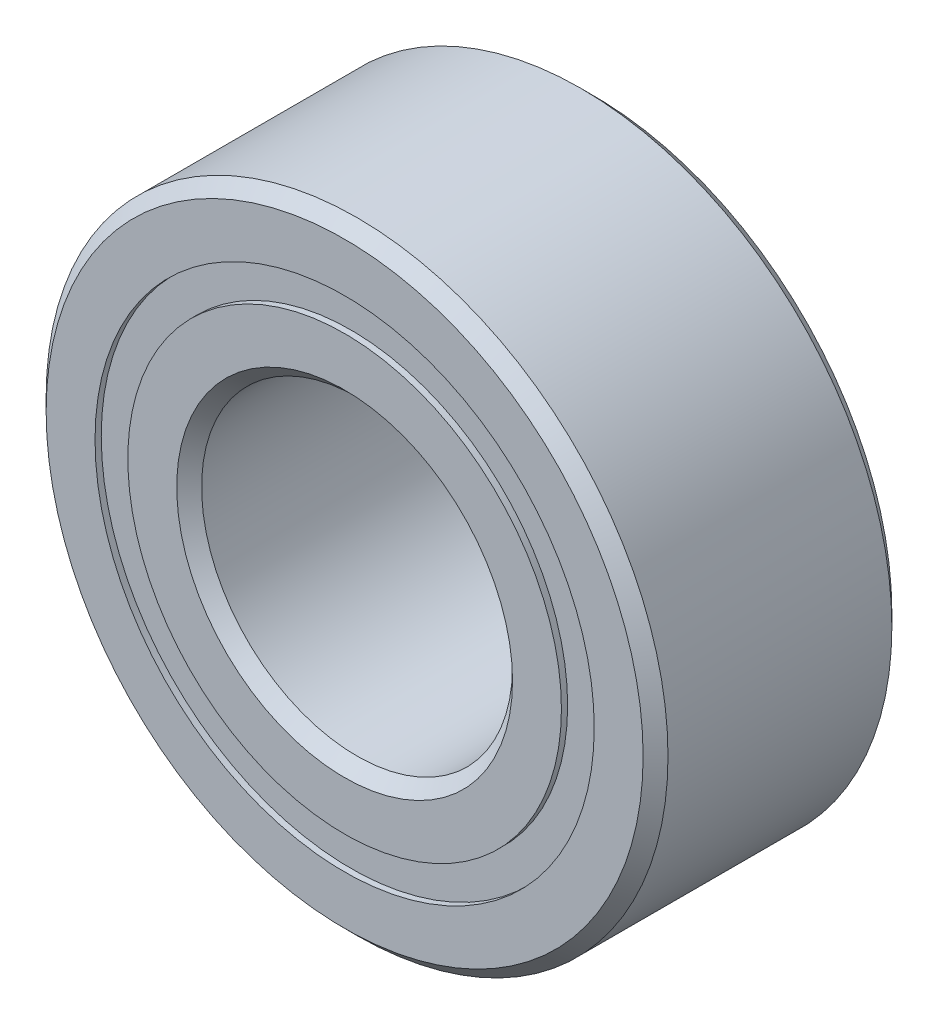
SolidWorks part; units mm, degrees
note: '?' marks a value the reader was unsure of.
ref_plane "Front Plane" through (0, 0, 0) normal (0, 0, 1) x (1, 0, 0)
ref_plane "Top Plane" through (0, 0, 0) normal (0, 1, 0) x (1, 0, 0)
ref_plane "Right Plane" through (0, 0, 0) normal (1, 0, 0) x (0, 0, -1)
sketch "Sketch1" plane through (0, 0, 0) normal (1, 0, 0) x (0, 0, -1)
  line L0 (-2, 0) -> (2, 0) construction
  line L1 (0, 5) -> (0, -5) construction
  line L2 (1.8, 5) -> (-1.8, 5)
  line L3 (-1.8, 5) -> (-2, 4.8)
  line L4 (-2, 4.8) -> (-2, 4.0137)
  line L5 (-2, 4.0137) -> (-0.8889, 4.0137)
  line L6 (2, 4.0137) -> (0.8889, 4.0137)
  line L7 (2, 4.8) -> (2, 4.0137)
  line L8 (1.8, 5) -> (2, 4.8)
  line L9 (0, 5) -> (0, 3.75) construction
  line L10 (0, 3.75) -> (0, 2.5) construction
  arc A0 (-0.8889, 4.0137) -> (0.8889, 4.0137) centre (0, 3.75) cw
  point P14 (0, 2.5)
  dimension "Width" = 4
  dimension "OD" = 10
  dimension "D1" = 45
  dimension "D2" = 0.2
  dimension "Shaft Dia" = 5
  dimension "D3" = 1.7778
  dimension "D4" = 0.2637
revolve "Revolve1" add sketch "Sketch1" angle 360 about L0
sketch "Sketch3" plane through (0, 0, 0) normal (1, 0, 0) x (0, 0, -1)
  line L0 (-2, 3.4863) -> (-0.8889, 3.4863)
  line L1 (0, 5) -> (0, -5) construction
  line L2 (-2, 4.8) -> (-2, 4.0137) construction
  line L3 (-2, 3.4863) -> (-2, 2.7)
  line L4 (-1.8, 5) -> (-2, 4.8) construction
  line L5 (-2, 2.7) -> (-1.8, 2.5)
  line L6 (-1.8, 2.5) -> (1.8, 2.5)
  line L7 (1.8, 5) -> (1.8, -5) construction
  line L8 (1.8, 2.5) -> (2, 2.7)
  line L9 (2, -4.8) -> (2, 4.8) construction
  line L10 (2, 2.7) -> (2, 3.4863)
  line L11 (2, 3.4863) -> (0.8889, 3.4863)
  line L13 (1.8, 5) -> (2, 4.8) construction
  arc A0 (0.8889, 4.0137) -> (-0.8889, 4.0137) centre (0, 3.75) ccw construction
  arc A1 (0.8889, 3.4863) -> (-0.8889, 3.4863) centre (0, 3.75) cw
revolve "Revolve3" add sketch "Sketch3" angle 360 about L0
sketch "Sketch4" plane through (0, 0, 0) normal (1, 0, 0) x (0, 0, -1)
  line L0 (-0.9272, 3.75) -> (0.9272, 3.75)
  arc A2 (-0.9272, 3.75) -> (0.9272, 3.75) centre (0, 3.75) cw
  arc A3 (0.8889, 4.0137) -> (-0.8889, 4.0137) centre (0, 3.75) ccw construction
revolve "Revolve4" add sketch "Sketch4" angle 360 about L0
ref_axis "Axis1" through (0, 0, -2) along (0, 0, 1)?
pattern_circular "CirPattern1" count 12 every 30 about axis through (0, 0, 0) along (0, 0, 1) of bodies 104
sketch "Sketch5" plane through (0, 0, 0) normal (1, 0, 0) x (0, 0, -1)
  line L0 (-2, 4.0137) -> (-0.8889, 4.0137) construction
  line L1 (-1.9, 4.0137) -> (-0.9272, 4.0137)
  line L2 (-1.9, 4.0137) -> (-1.9, 3.4863)
  line L3 (-1.9, 3.4863) -> (-0.9272, 3.4863)
  line L4 (-0.9272, 4.0137) -> (-0.9272, 3.4863)
  line L5 (-2, 3.4863) -> (-0.8889, 3.4863) construction
  line L6 (2, 4.0137) -> (0.8889, 4.0137) construction
  line L7 (1.9, 4.0137) -> (0.9272, 4.0137)
  line L8 (1.9, 4.0137) -> (1.9, 3.4863)
  line L9 (1.9, 3.4863) -> (0.9272, 3.4863)
  line L10 (0.9272, 4.0137) -> (0.9272, 3.4863)
  line L11 (2, 3.4863) -> (0.8889, 3.4863) construction
  line L12 (-1.8, 5) -> (-2, 4.8) construction
  point P18 (-1.9, 4.9)
revolve "Revolve5" add sketch "Sketch5" angle 360 about L0
sketch "Sketch6" plane through (0, 0, 0) normal (1, 0, 0) x (0, 0, -1)
  line L0 (2, 0) -> (-2, 0) construction
  line L1 (2, 4.0137) -> (0.9, 4.0137)
  line L2 (2, 4.0137) -> (2, 9.5)
  line L3 (2, 9.5) -> (0.9, 9.5)
  line L4 (0.9, 4.0137) -> (0.9, 9.5)
  dimension "Th" = 1.1
  dimension "Flange OD" = 19
revolve "Revolve6" [suppressed] add sketch "Sketch6" angle 360 about L0
equation "\"D2@Sketch1\" = \"Width@Sketch1\"*.05"
equation "\"D3@Sketch1\" = \"Width@Sketch1\"/2.25"
equation "\"D4@Sketch1\" = (((\"OD@Sketch1\"-\"Width@Sketch1\")/2)/3.25)/3.5"
equation "\"D2@CirPattern1\" = 360/\"Balls@CirPattern1\""
